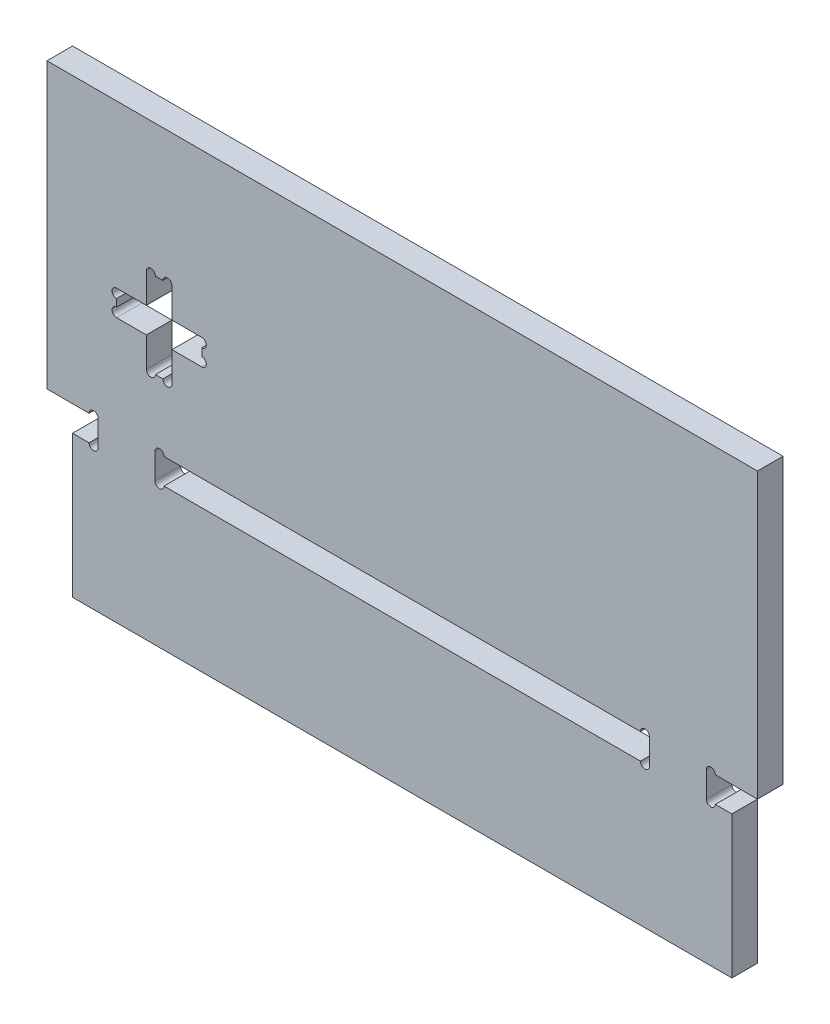
SolidWorks part; units mm, degrees
ref_plane "Piano frontale" through (0, 0, 0) normal (0, 0, 1) x (1, 0, 0)
ref_plane "Piano superiore" through (0, 0, 0) normal (0, 1, 0) x (1, 0, 0)
ref_plane "Piano destro" through (0, 0, 0) normal (1, 0, 0) x (0, 0, -1)
sketch "Schizzo1" plane through (0, 0, 0) normal (0, 0, 1) x (1, 0, 0)
  line L0 (-452.35, 100) -> (-464, 100)
  line L1 (0, 0) -> (-464, 0)
  line L2 (0, 0) -> (0, 100)
  line L3 (0, 100) -> (-11.65, 100)
  line L4 (-464, 0) -> (-464, 100)
  line L5 (-399.65, 118) -> (-64.35, 118)
  line L6 (-446, 118) -> (-446, 100)
  line L7 (-64.35, 100) -> (-399.65, 100)
  line L8 (-406, 118) -> (-406, 100)
  line L9 (-412.05, 185.92) -> (-433.05, 185.92)
  line L10 (-58, 118.0003) -> (-58, 100.0007)
  line L11 (-58, 109.0007) -> (-46.1442, 109.0007) construction
  line L12 (-18, 118.0007) -> (-18, 100)
  line L13 (-403.05, 194.92) -> (-446, 194.92) construction
  line L14 (-412.05, 203.92) -> (-433.05, 203.92)
  line L15 (-11.65, 118) -> (18, 118)
  line L16 (-482, 318) -> (18, 318)
  line L17 (-482, 318) -> (-482, 118)
  line L18 (-482, 118) -> (-452.35, 118)
  line L19 (18, 318) -> (18, 118)
  line L20 (-373.05, 185.92) -> (-394.05, 185.92)
  line L21 (-373.05, 192.27) -> (-373.05, 197.57)
  line L22 (-373.05, 203.92) -> (-394.05, 203.92)
  line L23 (-433.05, 192.27) -> (-433.05, 197.57)
  line L24 (-400.4, 224.92) -> (-405.7, 224.92)
  line L25 (-394.05, 224.92) -> (-394.05, 203.92)
  line L26 (-400.4, 164.92) -> (-405.7, 164.92)
  line L27 (-412.05, 224.92) -> (-412.05, 203.92)
  line L28 (-446, 194.92) -> (-403.05, 194.92) construction
  line L29 (-403.05, 194.92) -> (-403.05, 241.5653) construction
  line L30 (0, 100) -> (-464, 0) construction
  line L31 (-412.05, 185.92) -> (-412.05, 164.92)
  line L32 (-394.05, 185.92) -> (-394.05, 164.92)
  line L33 (-464, 100) -> (0, 0) construction
  line L34 (18, 318) -> (-482, 118) construction
  line L35 (-482, 318) -> (18, 118) construction
  line L36 (-232, 218) -> (-232, -92.9966) construction
  arc A0 (-406, 100) -> (-399.65, 100) centre (-402.825, 100) ccw
  arc A1 (-58, 100.0007) -> (-64.35, 100) centre (-61.175, 100.0003) cw
  arc A2 (-58, 118.0003) -> (-64.35, 118) centre (-61.175, 118) ccw
  arc A3 (-406, 118) -> (-399.65, 118) centre (-402.825, 118) cw
  arc A4 (-446, 100) -> (-452.35, 100) centre (-449.175, 100) cw
  arc A5 (-446, 118) -> (-452.35, 118) centre (-449.175, 118) ccw
  arc A6 (-18, 100) -> (-11.65, 100) centre (-14.825, 100) ccw
  arc A7 (-18, 118.0007) -> (-11.65, 118) centre (-14.825, 118) cw
  arc A8 (-394.05, 224.92) -> (-400.4, 224.92) centre (-397.225, 224.92) ccw
  arc A9 (-412.05, 224.92) -> (-405.7, 224.92) centre (-408.875, 224.92) cw
  arc A10 (-412.05, 164.92) -> (-405.7, 164.92) centre (-408.875, 164.92) ccw
  arc A11 (-394.05, 164.92) -> (-400.4, 164.92) centre (-397.225, 164.92) cw
  arc A12 (-373.05, 203.92) -> (-373.05, 197.57) centre (-373.05, 200.745) cw
  arc A13 (-373.05, 185.92) -> (-373.05, 192.27) centre (-373.05, 189.095) ccw
  arc A14 (-433.05, 185.92) -> (-433.05, 192.27) centre (-433.05, 189.095) cw
  arc A15 (-433.05, 203.92) -> (-433.05, 197.57) centre (-433.05, 200.745) ccw
  point P13 (-402.825, 121.175)
  point P14 (-403.05, 194.92)
  point P68 (-14.8247, 121.175)
  point P71 (-232, 50)
  dimension "D8" = 3.175
  dimension "D15" = 3.175
  dimension "D16" = 3.175
  dimension "D20" = 3.175
  dimension "D22" = 0
  dimension "D23" = 3.175
  dimension "D27" = 3.175
  dimension "D1" = 464
  dimension "D2" = 100
  dimension "D3" = 18
  dimension "D4" = 40
  dimension "D5" = 18
  dimension "D6" = 18
  dimension "D7" = 40
  dimension "D9" = 500
  dimension "D10" = 200
  dimension "D11" = 18
  dimension "D12" = 60
  dimension "D13" = 18
  dimension "D14" = 60
  dimension "D17" = 48.95
  dimension "D18" = 46.92
  dimension "D19" = 18
  dimension "D21" = 3.175
  dimension "D24" = 0
  dimension "D25" = 0
  dimension "D26" = 3.175
  dimension "D28" = 0
extrude "Estrusione-Estrusione1" add sketch "Schizzo1" along normal blind 18 contours L16 L19 L15 A7 L12 A6 L3 L2 L1 L4 L0 A4 L6 A5 L18 L17
extrude "Taglio-Estrusione3" cut sketch "Schizzo1<6>" along normal blind 61 contours L5 A2 L10 A1 L7 A0 L8 A3
sketch "Schizzo1<6>" plane through (0, 0, 0) normal (0, 0, 1) x (1, 0, 0) same geometry as "Schizzo1"
extrude "Taglio-Estrusione5" cut sketch "Schizzo1<8>" along normal blind 100 contours L27 L14 A15 L23 A14 L9 L31 A10 L26 A11 L32 L20 A13 L21 A12 L22 L25 A8 L24 A9
sketch "Schizzo1<8>" plane through (0, 0, 0) normal (0, 0, 1) x (1, 0, 0) same geometry as "Schizzo1"
